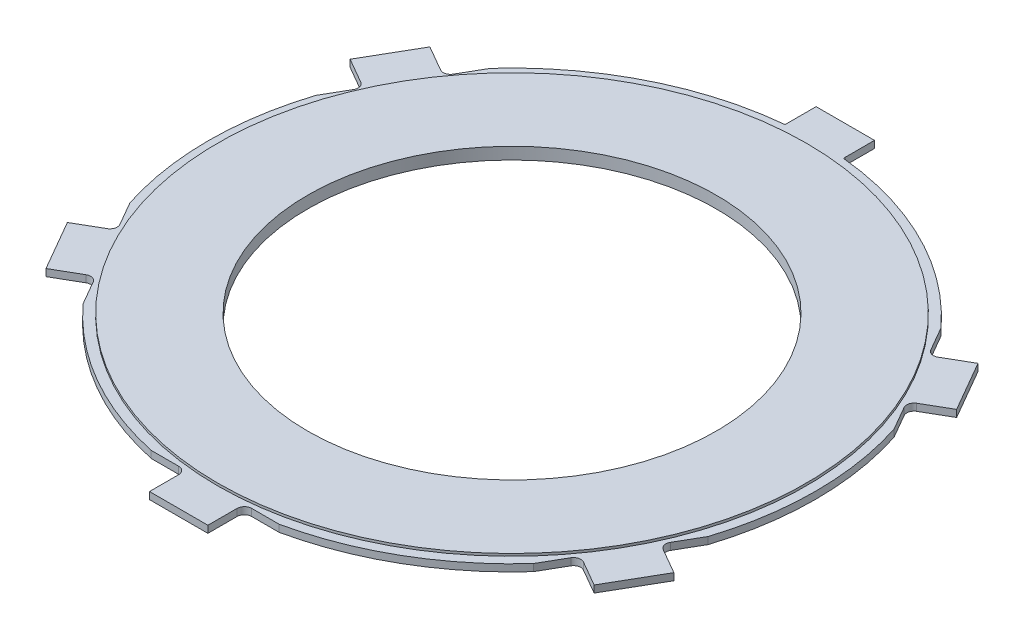
SolidWorks part; units mm, degrees
material "1.0060 (E335)"
ref_plane "Front Plane" through (0, 0, 0) normal (0, 0, 1) x (1, 0, 0)
ref_plane "Top Plane" through (0, 0, 0) normal (0, 1, 0) x (1, 0, 0)
ref_plane "Right Plane" through (0, 0, 0) normal (1, 0, 0) x (0, 0, -1)
sketch "Sketch1" plane through (0, 0, 0) normal (0, 1, 0) x (1, 0, 0)
  line L0 (0, -1000) -> (0, 49000) construction
  circle A0 centre (0, 0) radius 62.4
  circle A1 centre (0, 0) radius 42
  dimension "D1" = 124.8
  dimension "D2" = 84
extrude "Boss-Extrude1" add sketch "Sketch1" along normal mid plane 1.45
sketch "Sketch2" plane through (0, 0, 0) normal (0, 1, 0) x (1, 0, 0)
  line L0 (0, -1000) -> (0, 49000) construction
  line L1 (-6, 68.5) -> (6, 68.5)
  line L2 (6, 68.5) -> (6, 62.1109)
  line L3 (-6, 68.5) -> (-6, 62.1109)
  circle A0 centre (0, 0) radius 62.4 construction
  arc A1 (6, 62.1109) -> (-6, 62.1109) centre (0, 0) ccw
  point P8 (0, 68.5)
  dimension "D1" = 12
  dimension "D2" = 68.5
extrude "Boss-Extrude2" add sketch "Sketch2" along normal mid plane 1.45
sketch "Sketch4" plane through (0, 0, 0) normal (0, 1, 0) x (1, 0, 0)
  line L0 (0, -1000) -> (0, 49000) construction
  line L1 (-13.1438, 61) -> (-6, 61)
  line L2 (-6, 62.1109) -> (-6, 61)
  line L3 (6, 62.1109) -> (6, 61)
  line L4 (6, 61) -> (13.1438, 61)
  arc A0 (-6, 62.1109) -> (6, 62.1109) centre (0, 0) ccw construction
  arc A1 (-6, 62.1109) -> (6, 62.1109) centre (0, 0) ccw
  dimension "D1" = 61
extrude "Cut-Extrude2" cut sketch "Sketch4" against normal through all both and the other way through all contours L2 A1 L1 | L4 A1 L3 region at (-8.5165, 0, -61.3959) region at (8.5165, 0, -61.3959)
fillet "Fillet1" radius 1.5 2 edges at (6, 0, -61) (-6, 0, -61)
pattern_circular "CirPattern1" count 6 over 360 about axis through (0, 0.725, 0) along (0, 1, 0) of "Boss-Extrude1", "Fillet1", "Cut-Extrude2", "Boss-Extrude2"
sketch "Sketch5" plane through (0, 0, 0) normal (0, 1, 0) x (1, 0, 0)
  circle A0 centre (0, 0) radius 60.5
  circle A1 centre (0, 0) radius 42 construction
  circle A2 centre (0, 0) radius 42
  dimension "D1" = 121
extrude "Boss-Extrude3" add sketch "Sketch5" along normal blind 0.5 from surface starting at face at (0, 0.725, 2.5406)
extrude "Boss-Extrude5" add sketch "Sketch5<4>" against normal blind 0.5 from surface starting at face at (0, -0.725, 42)
sketch "Sketch5<4>" plane through (0, 0, 0) normal (0, 1, 0) x (1, 0, 0) same geometry as "Sketch5"
